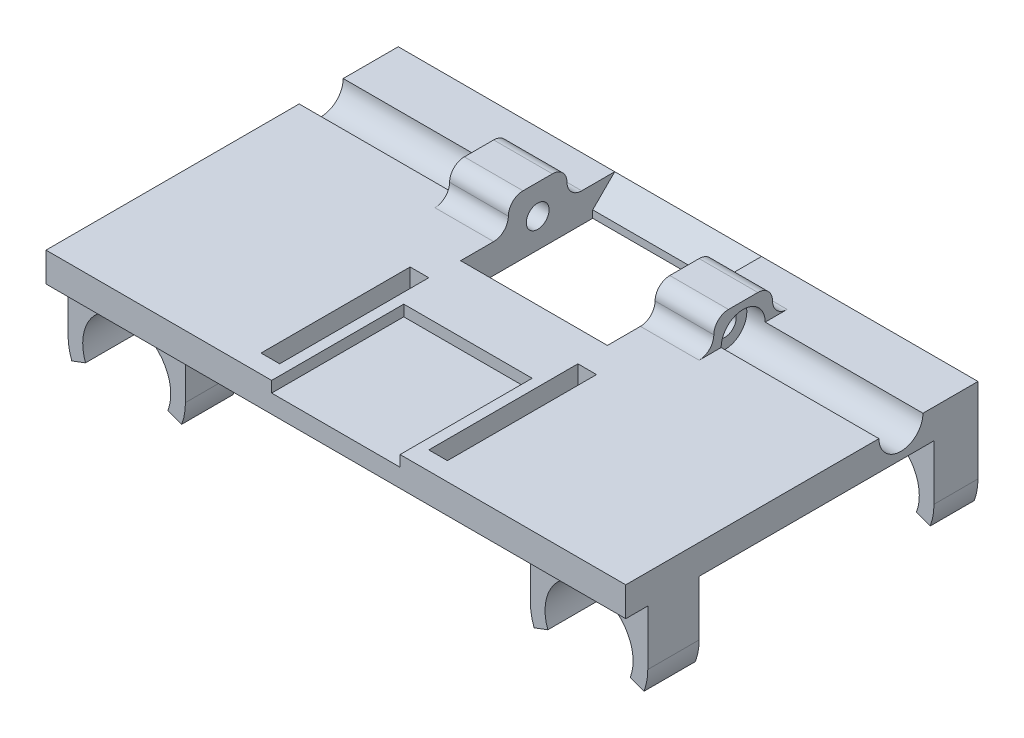
SolidWorks part; units mm, degrees
ref_plane "Спереди" through (0, 0, 0) normal (0, 0, 1) x (1, 0, 0)
ref_plane "Сверху" through (0, 0, 0) normal (0, 1, 0) x (1, 0, 0)
ref_plane "Справа" through (0, 0, 0) normal (1, 0, 0) x (0, 0, -1)
sketch "Эскиз1" plane through (0, 0, 0) normal (0, 1, 0) x (1, 0, 0)
  line L0 (29.34, 22.82) -> (49.66, 22.82) construction
  line L1 (0, 0) -> (79, 0)
  line L2 (0, 0) -> (0, 48)
  line L3 (0, 48) -> (79, 48)
  line L4 (79, 0) -> (79, 48)
  line L5 (26.8, 22.82) -> (29.34, 22.82)
  line L6 (26.8, 22.82) -> (26.8, 2.5)
  line L7 (26.8, 2.5) -> (29.34, 2.5)
  line L8 (29.34, 22.82) -> (29.34, 2.5)
  line L9 (49.66, 22.82) -> (52.2, 22.82)
  line L10 (49.66, 22.82) -> (49.66, 2.5)
  line L11 (49.66, 2.5) -> (52.2, 2.5)
  line L12 (52.2, 22.82) -> (52.2, 2.5)
  line L13 (49.66, 2.5) -> (29.34, 2.5) construction
  line L14 (39.5, 48) -> (39.5, 0) construction
  line L16 (29.5, 45) -> (49.5, 45)
  line L17 (29.5, 45) -> (29.5, 30)
  line L18 (29.5, 30) -> (49.5, 30)
  line L19 (49.5, 45) -> (49.5, 30)
  point P13 (28.07, 22.82)
  point P14 (50.93, 22.82)
  point P21 (39.5, 45)
  point P22 (39.5, 22.82)
  dimension "D1" = 48
  dimension "D2" = 79
  dimension "D3" = 22.86
  dimension "D4" = 20.32
  dimension "D5" = 2.5
  dimension "D6" = 2.54
  dimension "D7" = 20
  dimension "D8" = 15
  dimension "D9" = 3
extrude "Бобышка-Вытянуть1" add sketch "Эскиз1" along normal blind 4
sketch "Эскиз3" plane through (29.5, 0, 0) normal (1, 0, 0) x (0, 0, -1)
  line L0 (45, 4) -> (30, 4) construction
  line L2 (33.5, 4) -> (33.5, 8)
  line L3 (33.5, 8) -> (41.5, 8)
  line L4 (41.5, 4) -> (41.5, 8)
  line L5 (33.5, 4) -> (41.5, 4)
  point P6 (37.5, 4)
  point P7 (37.5, 8)
  dimension "D2" = 8
  dimension "D3" = 4
extrude "Бобышка-Вытянуть2" add sketch "Эскиз3" against normal blind 8
fillet "Скругление1" radius 2 4 edges at (25.5, 4, -41.5) (25.5, 8, -41.5) (25.5, 8, -33.5) (25.5, 4, -33.5)
sketch "Эскиз5" plane through (0, 0, 0) normal (-1, 0, 0) x (0, 0, 1)
  line L1 (-35.5, 8) -> (-39.5, 8) construction
  circle A0 centre (-37.5, 4) radius 3
  dimension "D2" = 6
  dimension "D1" = 4
extrude "Вырез-Вытянуть1" cut sketch "Эскиз5" against normal blind 24
sketch "Sketch2" plane through (49.5, 0, 0) normal (-1, 0, 0) x (0, 0, 1)
  line L0 (-30, 4) -> (-45, 4) construction
  line L2 (-41.5, 4) -> (-41.5, 8)
  line L3 (-41.5, 8) -> (-33.5, 8)
  line L4 (-33.5, 4) -> (-33.5, 8)
  line L5 (-41.5, 4) -> (-33.5, 4)
  point P6 (-37.5, 4)
  point P7 (-37.5, 8)
  dimension "D1" = 8
  dimension "D2" = 4
extrude "Boss-Extrude1" add sketch "Sketch2" against normal blind 8
fillet "Fillet1" radius 2 4 edges at (53.5, 8, -41.5) (53.5, 4, -41.5) (53.5, 4, -33.5) (53.5, 8, -33.5)
sketch "Sketch3" plane through (79, 0, 0) normal (1, 0, 0) x (0, 0, -1)
  line L0 (43.5, 4) -> (31.5, 4) construction
  circle A0 centre (37.5, 4) radius 3
  dimension "D1" = 6
extrude "Cut-Extrude2" cut sketch "Sketch3" against normal blind 24
chamfer "Chamfer1" distance 3 2 edges at (39.5, 4, -45) (39.5, 4, -30)
sketch "Sketch8" plane through (55, 0, 0) normal (1, 0, 0) x (0, 0, -1)
  circle A0 centre (37.5, 4) radius 1.55
  dimension "D1" = 3.1
extrude "Cut-Extrude5" cut sketch "Sketch8" against normal up to surface (31 mm away) up to face at (24, 4, -34.5)
sketch "Sketch9" plane through (0, 0, -48) normal (0, 0, -1) x (-1, 0, 0)
  line L0 (-39.5, 0) -> (-39.5, -34.0441) construction
  line L1 (-79, 0) -> (0, 0) construction
  line L2 (-79, 0) -> (-63, 0)
  line L3 (-79, 4) -> (-79, 0) construction
  line L4 (-79, 0) -> (-79, -7.5)
  line L5 (-63, 0) -> (-63, -7.5)
  line L6 (-63, 0) -> (-74.055, -10.3641) construction
  line L7 (-79, 0) -> (-65.9061, -11.8863) construction
  line L10 (-8, 0) -> (-8, -15.524) construction
  line L11 (-8, -7.5) -> (-0.6539, -10.2689) construction
  line L17 (-71, -7.5) -> (-78.3461, -10.2689) construction
  line L18 (-76.6144, -9.6162) -> (-78.4859, -10.3216)
  line L19 (-71, 0) -> (-71, -15.524) construction
  line L20 (-65.3856, -9.6162) -> (-63.5141, -10.3216)
  line L21 (0, 0) -> (-13.0939, -11.8863) construction
  line L22 (-16, 0) -> (-4.945, -10.3641) construction
  line L23 (-13.6144, -9.6162) -> (-15.4859, -10.3216)
  line L24 (-2.3856, -9.6162) -> (-0.5141, -10.3216)
  line L25 (-16, 0) -> (-16, -7.5)
  line L26 (0, 0) -> (0, -7.5)
  line L27 (0, 0) -> (-16, 0)
  arc A0 (-65.3856, -9.6162) -> (-76.6144, -9.6162) centre (-71, -7.5) ccw
  arc A1 (-63, -7.5) -> (-63.5141, -10.3216) centre (-71, -7.5) cw
  arc A2 (-78.4859, -10.3216) -> (-79, -7.5) centre (-71, -7.5) cw
  arc A6 (-0.5141, -10.3216) -> (0, -7.5) centre (-8, -7.5) ccw
  arc A7 (-16, -7.5) -> (-15.4859, -10.3216) centre (-8, -7.5) ccw
  arc A8 (-13.6144, -9.6162) -> (-2.3856, -9.6162) centre (-8, -7.5) cw
  point P11 (-71, 0)
  dimension "D2" = 12
  dimension "D1" = 16
  dimension "D3" = 7.5
  dimension "D4" = 22.5
extrude "Boss-Extrude4" add sketch "Sketch9" against normal blind 6
sketch "Sketch10" plane through (0, 4, 0) normal (0, 1, 0) x (1, 0, 0)
  line L0 (0, 0) -> (79, 0) construction
  line L1 (30.75, 0) -> (48.25, 0)
  line L2 (30.75, 0) -> (30.75, 18)
  line L3 (30.75, 18) -> (48.25, 18)
  line L4 (48.25, 0) -> (48.25, 18)
  line L5 (49.5, 27) -> (29.5, 27) construction
  point P8 (39.5, 27)
  point P9 (39.5, 18)
  dimension "D1" = 17.5
  dimension "D2" = 18
extrude "Cut-Extrude6" cut sketch "Sketch10" against normal blind 1.5
ref_plane "Plane1" through (0, 0, -10) normal (0, 0, 1) x (1, 0, 0)
sketch "Sketch13" plane through (0, 0, -10) normal (0, 0, 1) x (1, 0, 0)
  line L0 (39.5, 0) -> (39.5, -38.7249) construction
  line L1 (0, 0) -> (16, 0)
  line L2 (0, 0) -> (0, -7.5)
  line L3 (16, 0) -> (16, -7.5)
  line L4 (16, 0) -> (3.1003, -12.0935) construction
  line L5 (0, 0) -> (11.0939, -11.8863) construction
  line L8 (79, 0) -> (67.9061, -11.8863) construction
  line L9 (63, 0) -> (75.8997, -12.0935) construction
  line L12 (63, 0) -> (63, -7.5)
  line L13 (79, 0) -> (79, -7.5)
  line L14 (79, 0) -> (63, 0)
  line L15 (0, 0) -> (79, 0) construction
  line L16 (79, 4) -> (79, 0) construction
  line L17 (0.5141, -10.3216) -> (2.3856, -9.6162)
  line L18 (13.6144, -9.6162) -> (15.4859, -10.3216)
  line L19 (65.3856, -9.6162) -> (63.5141, -10.3216)
  line L20 (76.6144, -9.6162) -> (78.4859, -10.3216)
  arc A0 (13.6144, -9.6162) -> (2.3856, -9.6162) centre (8, -7.5) ccw
  arc A1 (16, -7.5) -> (15.4859, -10.3216) centre (8, -7.5) cw
  arc A2 (0.5141, -10.3216) -> (0, -7.5) centre (8, -7.5) cw
  arc A3 (78.4859, -10.3216) -> (79, -7.5) centre (71, -7.5) ccw
  arc A4 (63, -7.5) -> (63.5141, -10.3216) centre (71, -7.5) ccw
  arc A5 (65.3856, -9.6162) -> (76.6144, -9.6162) centre (71, -7.5) cw
  point P7 (8, 0)
  dimension "D3" = 7.5
extrude "Boss-Extrude5" add sketch "Sketch13" along normal blind 7
